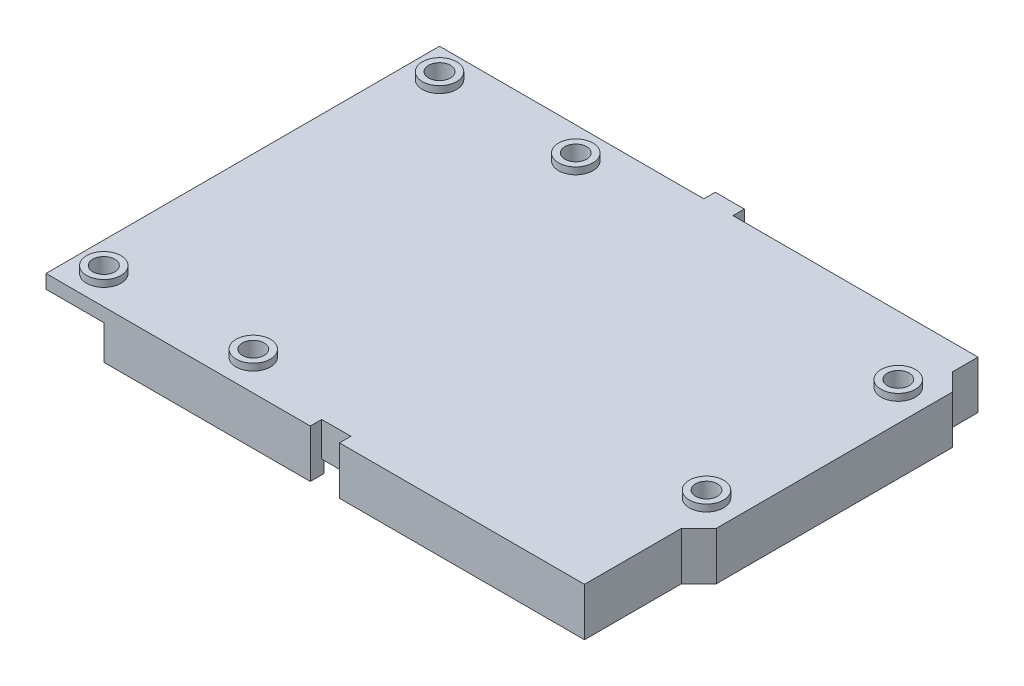
SolidWorks part; units mm, degrees
ref_plane "Front Plane" through (0, 0, 0) normal (0, 0, 1) x (1, 0, 0)
ref_plane "Top Plane" through (0, 0, 0) normal (0, 1, 0) x (1, 0, 0)
ref_plane "Right Plane" through (0, 0, 0) normal (1, 0, 0) x (0, 0, -1)
sketch "Sketch1" plane through (0, 0, 0) normal (0, 1, 0) x (1, 0, 0)
  line L0 (-2, 55.34) -> (-2, -2)
  line L1 (-2, -2) -> (68.04, -2)
  line L2 (68.04, -2) -> (68.04, 12.1256)
  line L3 (68.04, 12.1256) -> (70.58, 14.6656)
  line L4 (70.58, 14.6656) -> (70.58, 49.0884)
  line L5 (70.58, 49.0884) -> (68.04, 51.6284)
  line L6 (68.04, 51.6284) -> (68.04, 55.34)
  line L7 (68.04, 55.34) -> (-2, 55.34)
  line L8 (-2, 55.34) -> (-10.42, 55.34)
  line L9 (-10.42, 55.34) -> (-10.42, -2)
  line L10 (-10.42, -2) -> (-2, -2)
  line L11 (-6.21, 49.42) -> (-6.21, 3.92) construction
  line L12 (-10.42, 26.67) -> (-2, 26.67) construction
  line L13 (32.34, 55.34) -> (32.34, 57)
  line L14 (32.34, 57) -> (28.09, 57)
  line L15 (28.09, 57) -> (28.09, 55.34)
  line L16 (32.34, -2) -> (32.34, -0.34)
  line L17 (32.34, -0.34) -> (28.09, -0.34)
  line L18 (28.09, -0.34) -> (28.09, -2)
  line L19 (28.09, -0.34) -> (28.09, 55.34) construction
  line L20 (26.44, 0) -> (26.44, 1.31)
  line L21 (26.44, 1.31) -> (33.99, 1.31)
  line L22 (33.99, 1.31) -> (33.99, 0)
  line L23 (33.99, 1.31) -> (32.34, -0.34) construction
  line L24 (26.44, 1.31) -> (28.09, -0.34) construction
  line L25 (28.09, -0.34) -> (28.09, 0)
  line L27 (32.34, -0.34) -> (32.34, 0)
  point P14 (-6.21, 26.67)
  line B0 (66.04, 53.34) -> (0, 53.34)
  line B1 (0, 53.34) -> (0, 0)
  line B2 (0, 0) -> (66.04, 0)
  line B3 (66.04, 0) -> (66.04, 12.954)
  line B4 (66.04, 12.954) -> (68.58, 15.494)
  line B5 (68.58, 15.494) -> (68.58, 48.26)
  line B6 (68.58, 48.26) -> (66.04, 50.8)
  line B7 (66.04, 50.8) -> (66.04, 53.34)
  circle B8 centre (66.04, 17.78) radius 1.5875
  circle B9 centre (66.04, 45.72) radius 1.5875
  circle B10 centre (13.97, 50.8) radius 1.5875
  circle B11 centre (15.24, 2.54) radius 1.5875
  dimension "D10" = 45.5
  dimension "D1" = 2
  dimension "D2" = 2
  dimension "D3" = 2
  dimension "D4" = 2
  dimension "D5" = 2
  dimension "D6" = 2
  dimension "D7" = 2
  dimension "D8" = 2
  dimension "D9" = 81
  dimension "D11" = 4.25
  dimension "D12" = 59
  dimension "D13" = 35.7
  dimension "D14" = 57.34
  dimension "D15" = 45
  dimension "D16" = 45
  dimension "D17" = 1.65
sketch_block_instance "Block-arduino block-3"
sketch_block "Block-arduino block"
extrude "Boss-Extrude1" add sketch "Sketch1" against normal blind 2 contours B7 B6 B5 B4 B3 B2 L16 L1 L2 L3 L4 L5 L6 L7 L0 L18 B1 B0 | L9 L10 L0 L8 | B6 B7 B0 B1 B2 L17 B3 B4 B5 B11 B10 B9 B8 | L14 L15 L7 L13 | L20 B2 L22 L21 | B2 L25 L17 L27 region at (13.045, 0, -54.415) region at (-6.21, 0, -26.67) region at (30.215, 0, -56.17) region at (30.215, 0, 0.17) region at (30.215, 0, -0.655) region at (33.8234, 0, -26.8503)
extrude "Boss-Extrude2" add sketch "Sketch1<3>" against normal blind 5 from surface contours B7 B6 B5 B4 B3 B2 L16 L1 L2 L3 L4 L5 L6 L7 L0 L18 B1 B0 | L14 L15 L7 L13 region at (13.045, 0, -54.415) region at (30.215, 0, -56.17) starting at face at (39.6375, -2, -28.3868)
sketch "Sketch1<3>" plane through (0, 0, 0) normal (0, 1, 0) x (1, 0, 0) same geometry as "Sketch1"
sketch "Sketch2" plane through (0, 0, 0) normal (0, 1, 0) x (1, 0, 0)
  line L0 (-10.42, -2) -> (-2, -2) construction
  line L1 (-10.42, 55.34) -> (-6.21, 51.13) construction
  line L2 (-10.42, -2) -> (-6.21, 2.21) construction
  line L4 (-10.42, 55.34) -> (-10.42, -2) construction
  circle A0 centre (13.97, 50.8) radius 2.5
  circle A1 centre (66.04, 45.72) radius 2.5
  circle A2 centre (66.04, 17.78) radius 2.5
  circle A3 centre (15.24, 2.54) radius 2.5
  circle A4 centre (-6.21, 2.21) radius 2.5
  circle A5 centre (-6.21, 51.13) radius 2.5
  circle A6 centre (66.04, 45.72) radius 1.5875 construction
  circle A7 centre (66.04, 17.78) radius 1.5875 construction
  circle A8 centre (15.24, 2.54) radius 1.5875 construction
  circle A9 centre (13.97, 50.8) radius 1.5875 construction
  circle A10 centre (66.04, 45.72) radius 1.5875
  circle A11 centre (66.04, 17.78) radius 1.5875
  circle A12 centre (15.24, 2.54) radius 1.5875
  circle A13 centre (13.97, 50.8) radius 1.5875
  dimension "D1" = 5
  dimension "D2" = 45
  dimension "D3" = 45
extrude "Boss-Extrude3" add sketch "Sketch2" along normal blind 1
extrude "Boss-Extrude4" add sketch "Sketch1<4>" against normal blind 3 from surface contours B2 L25 L17 L27 | L20 B2 L22 L21 region at (30.215, 0, 0.17) region at (30.215, 0, -0.655) starting at face at (66.04, -2, -16.1925)
sketch "Sketch1<4>" plane through (0, 0, 0) normal (0, 1, 0) x (1, 0, 0) same geometry as "Sketch1"
sketch "Sketch3" plane through (0, -2, 0) normal (0, -1, 0) x (1, 0, 0)
  line L0 (12.74, 0) -> (12.74, -2.54)
  line L1 (0, 0) -> (26.44, 0) construction
  line L2 (17.74, -2.54) -> (17.74, 0)
  line L3 (0, 0) -> (28.09, 0) construction
  line L4 (17.74, 0) -> (12.74, 0)
  line L5 (16.47, -53.34) -> (16.47, -50.8)
  line L6 (66.04, -53.34) -> (0, -53.34) construction
  line L7 (11.47, -50.8) -> (11.47, -53.34)
  line L8 (66.04, -53.34) -> (0, -53.34) construction
  line L9 (11.47, -53.34) -> (16.47, -53.34)
  line L10 (68.58, -48.22) -> (66.04, -48.22)
  line L11 (68.58, -15.494) -> (68.58, -48.26) construction
  line L12 (66.04, -43.22) -> (68.58, -43.22)
  line L13 (68.58, -15.494) -> (68.58, -48.26) construction
  line L14 (68.58, -43.22) -> (68.58, -48.22)
  line L15 (68.58, -20.28) -> (66.04, -20.28)
  line L16 (66.04, -15.28) -> (68.58, -15.28)
  line L17 (68.58, -15.28) -> (68.58, -20.28)
  arc A0 (12.74, -2.54) -> (17.74, -2.54) centre (15.24, -2.54) ccw
  circle A1 centre (15.24, -2.54) radius 1.5875 construction
  circle A2 centre (15.24, -2.54) radius 2.5 construction
  circle A3 centre (15.24, -2.54) radius 1.5875
  arc A4 (16.47, -50.8) -> (11.47, -50.8) centre (13.97, -50.8) ccw
  circle A5 centre (13.97, -50.8) radius 1.5875 construction
  circle A6 centre (13.97, -50.8) radius 1.5875
  circle A8 centre (13.97, -50.8) radius 2.5 construction
  arc A9 (66.04, -48.22) -> (66.04, -43.22) centre (66.04, -45.72) cw
  circle A10 centre (66.04, -45.72) radius 1.5875 construction
  circle A11 centre (66.04, -45.72) radius 1.5875
  circle A12 centre (66.04, -45.72) radius 2.5 construction
  circle A13 centre (66.04, -17.78) radius 1.5875 construction
  circle A14 centre (66.04, -17.78) radius 1.5875
  arc A15 (66.04, -20.28) -> (66.04, -15.28) centre (66.04, -17.78) cw
  circle A16 centre (66.04, -17.78) radius 2.5 construction
extrude "Boss-Extrude5" add sketch "Sketch3" along normal up to surface (3 mm away) up to face at (30.215, -5, -0.2425)
hole_wizard "M3 Clearance Hole1" positions "Sketch6" profile "Sketch5" hole size "M3" standard "ANSI Metric" end condition up to next
sketch "Sketch6" plane through (0, 1, 0) normal (0, 1, 0) x (1, 0, 0)
  point P0 (-6.21, 51.13)
  point P3 (-6.21, 2.21)
sketch "Sketch5" plane through (-6.21, 1, -51.13) normal (1, 0, 0) x (0, 0, 1)
  line L0 (0, 0) -> (0, 3)
  line L1 (0, 3) -> (1.6, 3)
  line L2 (1.6, 3) -> (1.6, 0)
  line L5 (1.6, 0) -> (0, 0)
  line L11 (0, -6.35) -> (0, 107.95) construction
  dimension "Thru Hole Dia." = 3.2
  dimension "Thru Hole Depth" = 3
sketch "Sketch7" plane through (0, 0, 0) normal (0, 1, 0) x (1, 0, 0)
  line L23 (28.09, -0.34) -> (32.34, -0.34)
  line L24 (32.34, -0.34) -> (32.34, -2)
  line L25 (32.34, -2) -> (68.04, -2)
  line L26 (68.04, -2) -> (68.04, 12.1256)
  line L27 (68.04, 12.1256) -> (70.58, 14.6656)
  line L28 (70.58, 14.6656) -> (70.58, 49.0884)
  line L29 (70.58, 49.0884) -> (68.04, 51.6284)
  line L30 (68.04, 51.6284) -> (68.04, 55.34)
  line L31 (68.04, 55.34) -> (32.34, 55.34)
  line L32 (32.34, 55.34) -> (32.34, 57)
  line L33 (32.34, 57) -> (28.09, 57)
  line L34 (28.09, 57) -> (28.09, 55.34)
  line L35 (28.09, 55.34) -> (-10.42, 55.34)
  line L36 (-10.42, 55.34) -> (-10.42, -2)
  line L37 (-10.42, -2) -> (28.09, -2)
  line L38 (28.09, -2) -> (28.09, -0.34)
  line L39 (28.09, -0.34) -> (32.34, -0.34)
  line L40 (32.34, -0.34) -> (32.34, -2)
  line L41 (32.34, -2) -> (68.04, -2)
  line L42 (68.04, -2) -> (68.04, 12.1256)
  line L43 (68.04, 12.1256) -> (70.58, 14.6656)
  line L44 (70.58, 14.6656) -> (70.58, 49.0884)
  line L45 (70.58, 49.0884) -> (68.04, 51.6284)
  line L46 (68.04, 51.6284) -> (68.04, 55.34)
  line L47 (68.04, 55.34) -> (32.34, 55.34)
  line L48 (32.34, 55.34) -> (32.34, 57)
  line L49 (32.34, 57) -> (28.09, 57)
  line L50 (28.09, 57) -> (28.09, 55.34)
  line L51 (28.09, 55.34) -> (-10.42, 55.34)
  line L52 (-10.42, 55.34) -> (-10.42, -2)
  line L53 (-10.42, -2) -> (28.09, -2)
  line L54 (28.09, -2) -> (28.09, -0.34)
  circle A0 centre (15.24, 2.54) radius 1.5875 construction
  circle A1 centre (66.04, 17.78) radius 1.5875 construction
  circle A2 centre (66.04, 45.72) radius 1.5875 construction
  circle A3 centre (13.97, 50.8) radius 1.5875 construction
  circle A4 centre (-6.21, 2.21) radius 1.6 construction
  circle A5 centre (-6.21, 51.13) radius 1.6 construction
  circle A6 centre (15.24, 2.54) radius 1.5875
  circle A7 centre (66.04, 17.78) radius 1.5875
  circle A8 centre (66.04, 45.72) radius 1.5875
  circle A9 centre (13.97, 50.8) radius 1.5875
  circle A10 centre (-6.21, 2.21) radius 1.6
  circle A11 centre (-6.21, 51.13) radius 1.6
  dimension "D1" = 0
